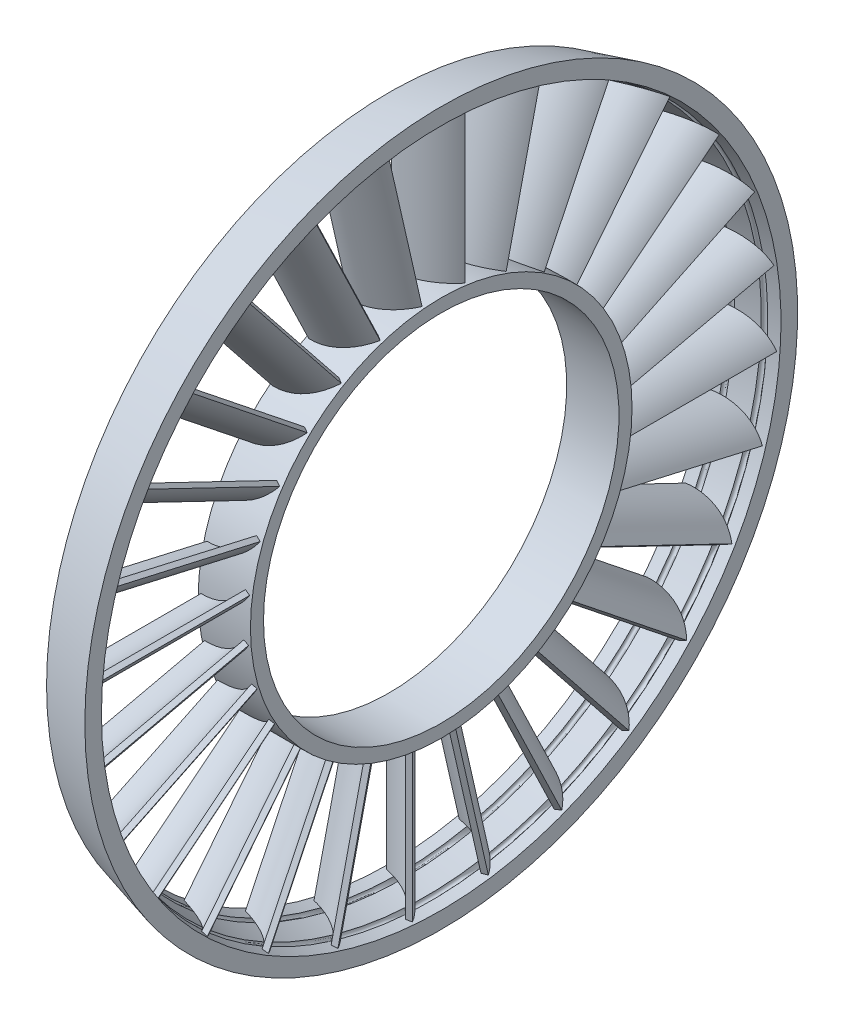
SolidWorks part; units mm, degrees
ref_plane "Front Plane" through (0, 0, 0) normal (0, 0, 1) x (1, 0, 0)
ref_plane "Top Plane" through (0, 0, 0) normal (0, 1, 0) x (1, 0, 0)
ref_plane "Right Plane" through (0, 0, 0) normal (1, 0, 0) x (0, 0, -1)
sketch "Sketch1" plane through (0, 0, 0) normal (0, 0, 1) x (1, 0, 0)
  line L0 (0, 18.6943) -> (0, -24.6443) construction
  line L1 (-41.248, 0) -> (50.0122, 0) construction
  line L2 (0, 18.6943) -> (0, 336.3839) construction
  line L3 (-10, 68) -> (10, 68)
  line L4 (-10, 68) -> (-10, 73)
  line L5 (-10, 73) -> (10, 73)
  line L6 (10, 68) -> (10, 73)
  line L7 (-10, 68) -> (10, 73) construction
  line L8 (-10, 73) -> (10, 68) construction
  line L9 (-10, 73) -> (-10, 172.8131) construction
  line L10 (10, 73) -> (10, 172.8131) construction
  line L11 (-10, 131) -> (10, 136.359)
  line L12 (-10, 124.64) -> (-5.9659, 125.7209)
  line L13 (-10, 124.64) -> (-10, 131)
  line L14 (10, 129.999) -> (10, 136.359)
  line L15 (-4.0341, 126.2386) -> (4.0341, 128.4004)
  line L16 (5.9659, 128.9181) -> (10, 129.999)
  arc A0 (-4.0341, 126.2386) -> (-5.9659, 125.7209) centre (-5, 125.9797) ccw
  arc A1 (5.9659, 128.9181) -> (4.0341, 128.4004) centre (5, 128.6592) ccw
  point P5 (0, 70.5)
  dimension "D7" = 2
  dimension "D8" = 2
  dimension "D1" = 5
  dimension "D2" = 20
  dimension "D3" = 68
  dimension "D4" = 131
  dimension "D5" = 15
  dimension "D9" = 5
  dimension "D10" = 5
sketch "Sketch3" plane through (0, 0, 0) normal (1, 0, 0) x (0, 0, -1)
  circle A0 centre (0, 0) radius 75.89
revolve "Revolve1" add sketch "Sketch1" angle 360 about L1
sketch "Sketch4" plane through (0, 0, 0) normal (0, 0, 1) x (1, 0, 0)
  line L0 (-10.9439, 0) -> (11.7505, 0) construction
  line L1 (10, -136.359) -> (10, 136.359) construction
  line L2 (-10, 131) -> (-10, -131) construction
  arc A0 (-9, 0) -> (9, -10) centre (-8.4059, -20.1307) cw
  point P3 (-9, 0)
  point P4 (9, -10)
  dimension "D1" = 1
  dimension "D2" = 1
  dimension "D3" = 10
extrude "Extrude-Thin1" add sketch "Sketch4" against normal up to surface (124.9078 mm away) thin up to face at (4.0341, 0, 128.4004) thin type one direction wall 2
pattern_circular "CirPattern1" count 28 over 360 about axis through (-41.248, 0, 0) along (-1, 0, 0) of "Extrude-Thin1"
sketch "Sketch5" plane through (0, 0, 0) normal (1, 0, 0) x (0, 0, -1)
  circle A0 centre (0, 0) radius 68
extrude "Cut-Extrude1" cut sketch "Sketch5" against normal mid plane 80
